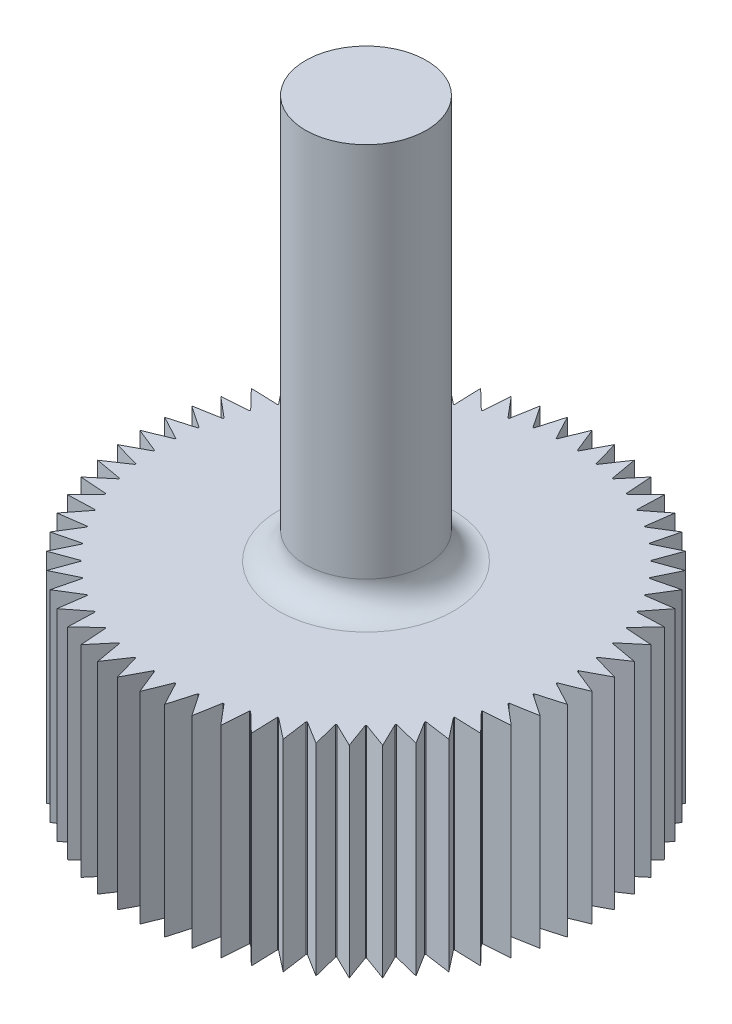
SolidWorks part; units mm, degrees
ref_plane "Plan de face" through (0, 0, 0) normal (0, 0, 1) x (1, 0, 0)
ref_plane "Plan de dessus" through (0, 0, 0) normal (0, 1, 0) x (1, 0, 0)
ref_plane "Plan de droite" through (0, 0, 0) normal (1, 0, 0) x (0, 0, -1)
sketch "Sketch2" plane through (0, 0, 0) normal (0, 1, 0) x (1, 0, 0)
  line L0 (-0.75, 14.9812) -> (0, 16.8353)
  line L1 (0, 16.8353) -> (0.75, 14.9812)
  line L2 (1.7598, 16.7431) -> (2.3119, 14.8208)
  line L3 (0.8201, 14.9776) -> (1.7598, 16.7431)
  line L4 (3.5003, 16.4674) -> (3.8484, 14.4979)
  line L5 (2.3812, 14.8098) -> (3.5003, 16.4674)
  line L6 (5.2024, 16.0113) -> (5.3427, 14.0162)
  line L7 (3.9162, 14.4798) -> (5.2024, 16.0113)
  line L8 (6.8475, 15.3798) -> (6.7786, 13.381)
  line L9 (5.4083, 13.9911) -> (6.8475, 15.3798)
  line L10 (8.4176, 14.5798) -> (8.1401, 12.5991)
  line L11 (6.8411, 13.3491) -> (8.4176, 14.5798)
  line L12 (9.8955, 13.62) -> (9.4125, 11.6792)
  line L13 (8.199, 12.5609) -> (9.8955, 13.62)
  line L14 (11.265, 12.5111) -> (10.5818, 10.6314)
  line L15 (9.467, 11.6351) -> (11.265, 12.5111)
  line L16 (12.5111, 11.265) -> (11.6351, 9.467)
  line L17 (10.6314, 10.5818) -> (12.5111, 11.265)
  line L18 (13.62, 9.8955) -> (12.5609, 8.199)
  line L19 (11.6792, 9.4125) -> (13.62, 9.8955)
  line L20 (14.5798, 8.4176) -> (13.3491, 6.8411)
  line L21 (12.5991, 8.1401) -> (14.5798, 8.4176)
  line L22 (15.3798, 6.8475) -> (13.9911, 5.4083)
  line L23 (13.381, 6.7786) -> (15.3798, 6.8475)
  line L24 (16.0113, 5.2024) -> (14.4798, 3.9162)
  line L25 (14.0162, 5.3427) -> (16.0113, 5.2024)
  line L26 (16.4674, 3.5003) -> (14.8098, 2.3812)
  line L27 (14.4979, 3.8484) -> (16.4674, 3.5003)
  line L28 (16.7431, 1.7598) -> (14.9776, 0.8201)
  line L29 (14.8208, 2.3119) -> (16.7431, 1.7598)
  line L30 (16.8353, 0) -> (14.9812, -0.75)
  line L31 (14.9812, 0.75) -> (16.8353, 0)
  line L32 (16.7431, -1.7598) -> (14.8208, -2.3119)
  line L33 (14.9776, -0.8201) -> (16.7431, -1.7598)
  line L34 (16.4674, -3.5003) -> (14.4979, -3.8484)
  line L35 (14.8098, -2.3812) -> (16.4674, -3.5003)
  line L36 (16.0113, -5.2024) -> (14.0162, -5.3427)
  line L37 (14.4798, -3.9162) -> (16.0113, -5.2024)
  line L38 (15.3798, -6.8475) -> (13.381, -6.7786)
  line L39 (13.9911, -5.4083) -> (15.3798, -6.8475)
  line L40 (14.5798, -8.4176) -> (12.5991, -8.1401)
  line L41 (13.3491, -6.8411) -> (14.5798, -8.4176)
  line L42 (13.62, -9.8955) -> (11.6792, -9.4125)
  line L43 (12.5609, -8.199) -> (13.62, -9.8955)
  line L44 (12.5111, -11.265) -> (10.6314, -10.5818)
  line L45 (11.6351, -9.467) -> (12.5111, -11.265)
  line L46 (11.265, -12.5111) -> (9.467, -11.6351)
  line L47 (10.5818, -10.6314) -> (11.265, -12.5111)
  line L48 (9.8955, -13.62) -> (8.199, -12.5609)
  line L49 (9.4125, -11.6792) -> (9.8955, -13.62)
  line L50 (8.4176, -14.5798) -> (6.8411, -13.3491)
  line L51 (8.1401, -12.5991) -> (8.4176, -14.5798)
  line L52 (6.8475, -15.3798) -> (5.4083, -13.9911)
  line L53 (6.7786, -13.381) -> (6.8475, -15.3798)
  line L54 (5.2024, -16.0113) -> (3.9162, -14.4798)
  line L55 (5.3427, -14.0162) -> (5.2024, -16.0113)
  line L56 (3.5003, -16.4674) -> (2.3812, -14.8098)
  line L57 (3.8484, -14.4979) -> (3.5003, -16.4674)
  line L58 (1.7598, -16.7431) -> (0.8201, -14.9776)
  line L59 (2.3119, -14.8208) -> (1.7598, -16.7431)
  line L60 (0, -16.8353) -> (-0.75, -14.9812)
  line L61 (0.75, -14.9812) -> (0, -16.8353)
  line L62 (-1.7598, -16.7431) -> (-2.3119, -14.8208)
  line L63 (-0.8201, -14.9776) -> (-1.7598, -16.7431)
  line L64 (-3.5003, -16.4674) -> (-3.8484, -14.4979)
  line L65 (-2.3812, -14.8098) -> (-3.5003, -16.4674)
  line L66 (-5.2024, -16.0113) -> (-5.3427, -14.0162)
  line L67 (-3.9162, -14.4798) -> (-5.2024, -16.0113)
  line L68 (-6.8475, -15.3798) -> (-6.7786, -13.381)
  line L69 (-5.4083, -13.9911) -> (-6.8475, -15.3798)
  line L70 (-8.4176, -14.5798) -> (-8.1401, -12.5991)
  line L71 (-6.8411, -13.3491) -> (-8.4176, -14.5798)
  line L72 (-9.8955, -13.62) -> (-9.4125, -11.6792)
  line L73 (-8.199, -12.5609) -> (-9.8955, -13.62)
  line L74 (-11.265, -12.5111) -> (-10.5818, -10.6314)
  line L75 (-9.467, -11.6351) -> (-11.265, -12.5111)
  line L76 (-12.5111, -11.265) -> (-11.6351, -9.467)
  line L77 (-10.6314, -10.5818) -> (-12.5111, -11.265)
  line L78 (-13.62, -9.8955) -> (-12.5609, -8.199)
  line L79 (-11.6792, -9.4125) -> (-13.62, -9.8955)
  line L80 (-14.5798, -8.4176) -> (-13.3491, -6.8411)
  line L81 (-12.5991, -8.1401) -> (-14.5798, -8.4176)
  line L82 (-15.3798, -6.8475) -> (-13.9911, -5.4083)
  line L83 (-13.381, -6.7786) -> (-15.3798, -6.8475)
  line L84 (-16.0113, -5.2024) -> (-14.4798, -3.9162)
  line L85 (-14.0162, -5.3427) -> (-16.0113, -5.2024)
  line L86 (-16.4674, -3.5003) -> (-14.8098, -2.3812)
  line L87 (-14.4979, -3.8484) -> (-16.4674, -3.5003)
  line L88 (-16.7431, -1.7598) -> (-14.9776, -0.8201)
  line L89 (-14.8208, -2.3119) -> (-16.7431, -1.7598)
  line L90 (-16.8353, 0) -> (-14.9812, 0.75)
  line L91 (-14.9812, -0.75) -> (-16.8353, 0)
  line L92 (-16.7431, 1.7598) -> (-14.8208, 2.3119)
  line L93 (-14.9776, 0.8201) -> (-16.7431, 1.7598)
  line L94 (-16.4674, 3.5003) -> (-14.4979, 3.8484)
  line L95 (-14.8098, 2.3812) -> (-16.4674, 3.5003)
  line L96 (-16.0113, 5.2024) -> (-14.0162, 5.3427)
  line L97 (-14.4798, 3.9162) -> (-16.0113, 5.2024)
  line L98 (-15.3798, 6.8475) -> (-13.381, 6.7786)
  line L99 (-13.9911, 5.4083) -> (-15.3798, 6.8475)
  line L100 (-14.5798, 8.4176) -> (-12.5991, 8.1401)
  line L101 (-13.3491, 6.8411) -> (-14.5798, 8.4176)
  line L102 (-13.62, 9.8955) -> (-11.6792, 9.4125)
  line L103 (-12.5609, 8.199) -> (-13.62, 9.8955)
  line L104 (-12.5111, 11.265) -> (-10.6314, 10.5818)
  line L105 (-11.6351, 9.467) -> (-12.5111, 11.265)
  line L106 (-11.265, 12.5111) -> (-9.467, 11.6351)
  line L107 (-10.5818, 10.6314) -> (-11.265, 12.5111)
  line L108 (-9.8955, 13.62) -> (-8.199, 12.5609)
  line L109 (-9.4125, 11.6792) -> (-9.8955, 13.62)
  line L110 (-8.4176, 14.5798) -> (-6.8411, 13.3491)
  line L111 (-8.1401, 12.5991) -> (-8.4176, 14.5798)
  line L112 (-6.8475, 15.3798) -> (-5.4083, 13.9911)
  line L113 (-6.7786, 13.381) -> (-6.8475, 15.3798)
  line L114 (-5.2024, 16.0113) -> (-3.9162, 14.4798)
  line L115 (-5.3427, 14.0162) -> (-5.2024, 16.0113)
  line L116 (-3.5003, 16.4674) -> (-2.3812, 14.8098)
  line L117 (-3.8484, 14.4979) -> (-3.5003, 16.4674)
  line L118 (-1.7598, 16.7431) -> (-0.8201, 14.9776)
  line L119 (-2.3119, 14.8208) -> (-1.7598, 16.7431)
  circle A0 centre (0, 0) radius 15
  circle A1 centre (0, 0) radius 4
  circle A2 centre (0, 0) radius 4.5
  dimension "D3" = 30
  dimension "D6" = 8
  dimension "D7" = 9
  dimension "D1" = 2
  dimension "D2" = 2
  dimension "D4" = 1.5
  dimension "D5" = 60
extrude "Boss-Extrude1" add sketch "Sketch2" along normal blind 15 contours A0 | A0 L64 L65 | A0 L66 L67 | A0 L68 L69 | A0 L70 L71 | A0 L72 L73 | A0 L74 L75 | A0 L76 L77 | A0 L78 L79 | A0 L80 L81 | A0 L82 L83 | A0 L84 L85 | A0 L86 L87 | A0 L88 L89 | A0 L90 L91 | A0 L92 L93 | A0 L94 L95 | A0 L96 L97 | A0 L98 L99 | A0 L100 L101 | A0 L102 L103 | A0 L104 L105 | A0 L106 L107 | A0 L108 L109 | A0 L110 L111 | A0 L112 L113 | A0 L114 L115 | A0 L116 L117 | A0 L118 L119 | A0 L1 L0 | A0 L2 L3 | A0 L4 L5 | A0 L6 L7 | A0 L8 L9 | A0 L10 L11 | A0 L12 L13 | A0 L14 L15 | A0 L16 L17 | A0 L18 L19 | A0 L20 L21 | A0 L24 L25 | A0 L22 L23 | A0 L26 L27 | A0 L28 L29 | A0 L30 L31 | A0 L32 L33 | A0 L34 L35 | A0 L36 L37 | A0 L38 L39 | A0 L40 L41 | A0 L42 L43 | A0 L44 L45 | A0 L46 L47 | A0 L48 L49 | A0 L50 L51 | A0 L52 L53 | A0 L54 L55 | A0 L56 L57 | A0 L58 L59 | A0 L60 L61 | A0 L62 L63 | A2 A1 region at (0, 0, -15.6076) region at (0, 0, -14.5757) region at (-1.6314, 0, -15.5221) region at (1.6314, 0, -15.5221) region at (-3.245, 0, -15.2665) region at (3.245, 0, -15.2665) region at (-4.823, 0, -14.8437) region at (4.823, 0, -14.8437) region at (-6.3482, 0, -14.2583) region at (6.3482, 0, -14.2583) region at (-7.8038, 0, -13.5166) region at (7.8038, 0, -13.5166) region at (-9.1739, 0, -12.6268) region at (9.1739, 0, -12.6268) region at (-10.4435, 0, -11.5987) region at (10.4435, 0, -11.5987) region at (-11.5987, 0, -10.4435) region at (11.5987, 0, -10.4435) region at (-12.6268, 0, -9.1739) region at (12.6268, 0, -9.1739) region at (-13.5166, 0, -7.8038) region at (13.5166, 0, -7.8038) region at (-14.2583, 0, -6.3482) region at (14.2583, 0, -6.3482) region at (-14.8437, 0, -4.823) region at (14.8437, 0, -4.823) region at (-15.2665, 0, -3.245) region at (15.2665, 0, -3.245) region at (-15.5221, 0, -1.6314) region at (15.5221, 0, -1.6314) region at (-15.6076, 0, 0) region at (15.6076, 0, 0) region at (-15.5221, 0, 1.6314) region at (15.5221, 0, 1.6314) region at (-15.2665, 0, 3.245) region at (15.2665, 0, 3.245) region at (-14.8437, 0, 4.823) region at (14.8437, 0, 4.823) region at (-14.2583, 0, 6.3482) region at (14.2583, 0, 6.3482) region at (-13.5166, 0, 7.8038) region at (13.5166, 0, 7.8038) region at (-12.6268, 0, 9.1739) region at (12.6268, 0, 9.1739) region at (-11.5987, 0, 10.4435) region at (11.5987, 0, 10.4435) region at (-10.4435, 0, 11.5987) region at (10.4435, 0, 11.5987) region at (-9.1739, 0, 12.6268) region at (9.1739, 0, 12.6268) region at (-7.8038, 0, 13.5166) region at (7.8038, 0, 13.5166) region at (-6.3482, 0, 14.2583) region at (6.3482, 0, 14.2583) region at (-4.823, 0, 14.8437) region at (4.823, 0, 14.8437) region at (-3.245, 0, 15.2665) region at (3.245, 0, 15.2665) region at (-1.6314, 0, 15.5221) region at (1.6314, 0, 15.5221)
extrude "Boss-Extrude2" add sketch "Sketch2<3>" along normal blind 30 and the other way blind 1 from surface separate body contours A2 starting at face at (0, 15, 0)
sketch "Sketch2<3>" plane through (0, 0, 0) normal (0, 1, 0) x (1, 0, 0) same geometry as "Sketch2"
combine bodies "Combine1" operation type add bodies to combine 101 102
fillet "Fillet1" radius 2 1 edges at (0, 15, 4.5)
